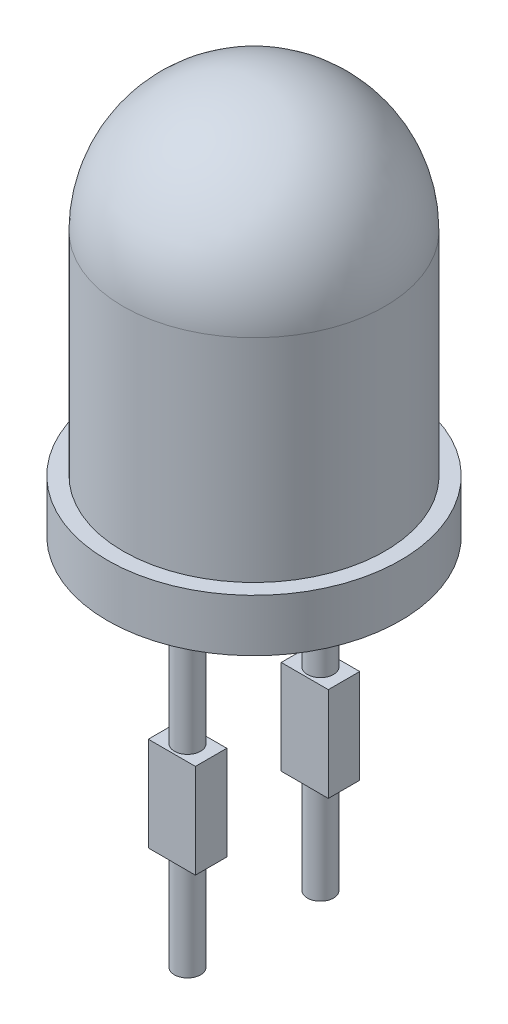
SolidWorks part; units mm, degrees
ref_plane "Front Plane" through (0, 0, 0) normal (0, 0, 1) x (1, 0, 0)
ref_plane "Top Plane" through (0, 0, 0) normal (0, 1, 0) x (1, 0, 0)
ref_plane "Right Plane" through (0, 0, 0) normal (1, 0, 0) x (0, 0, -1)
sketch "Sketch1" plane through (0, 0, 0) normal (1, 0, 0) x (0, 0, -1)
  line L0 (0, 4.525) -> (0, -10.9525) construction
  line L1 (-2.5, 2.025) -> (-2.5, -2.025)
  line L2 (-2.5, -2.025) -> (-2.8, -2.025)
  line L3 (-2.8, -2.025) -> (-2.8, -3.025)
  line L4 (-2.8, -3.025) -> (0, -3.025)
  line L5 (0, 4.525) -> (-4.2269, 4.525) construction
  line L6 (0, 4.525) -> (0, -3.025)
  arc A0 (-2.5, 2.025) -> (0, 4.525) centre (0, 2.025) cw
  point P11 (-2.5, 0)
  dimension "D1" = 5
  dimension "D2" = 7.55
  dimension "D3" = 1
  dimension "D4" = 5.6
revolve "Revolve1" add sketch "Sketch1" angle 360 about L0
sketch "Sketch2" plane through (0, -3.025, 0) normal (0, -1, 0) x (1, 0, 0)
  line L0 (0, 0) -> (3.908, 0) construction
  circle A0 centre (0, 1.27) radius 0.25
  circle A1 centre (0, -1.27) radius 0.25
  dimension "D1" = 2.54
  dimension "D2" = 0.5
extrude "Boss-Extrude1" add sketch "Sketch2" along normal blind 11 separate body
sketch "Sketch3" plane through (0, 0, 0) normal (1, 0, 0) x (0, 0, -1)
  line L0 (1.27, -3.025) -> (1.27, -15.6133) construction
  line L1 (0.97, -5.825) -> (1.57, -5.825)
  line L2 (0.97, -5.825) -> (0.97, -7.625)
  line L3 (0.97, -7.625) -> (1.57, -7.625)
  line L4 (1.57, -5.825) -> (1.57, -7.625)
  line L5 (0.97, -5.825) -> (1.57, -7.625) construction
  line L6 (0.97, -7.625) -> (1.57, -5.825) construction
  line L7 (1.52, -3.025) -> (1.02, -3.025) construction
  line L8 (-2.8, -3.025) -> (2.8, -3.025) construction
  line L9 (0, 0) -> (0, -3.6509) construction
  line L10 (-0.97, -7.625) -> (-1.57, -7.625)
  line L11 (-1.57, -5.825) -> (-1.57, -7.625)
  line L12 (-0.97, -5.825) -> (-1.57, -5.825)
  line L13 (-0.97, -5.825) -> (-0.97, -7.625)
  point P0 (1.27, -6.725)
  dimension "D1" = 0.6
  dimension "D2" = 2.8
  dimension "D3" = 1.8
extrude "Boss-Extrude2" add sketch "Sketch3" along normal mid plane 0.9
sketch "Sketch4" plane through (0, 0, 0) normal (0, 0, 1) x (1, 0, 0)
  line L0 (-2.8, -3.025) -> (2.8, -3.025) construction
  line L1 (-3.6103, -9.525) -> (4.2381, -9.525)
  line L2 (-3.6103, -9.525) -> (-3.6103, -15.2177)
  line L3 (-3.6103, -15.2177) -> (4.2381, -15.2177)
  line L4 (4.2381, -9.525) -> (4.2381, -15.2177)
  dimension "D1" = 6.5
extrude "Cut-Extrude1" cut sketch "Sketch4" against normal through all both and the other way through all
